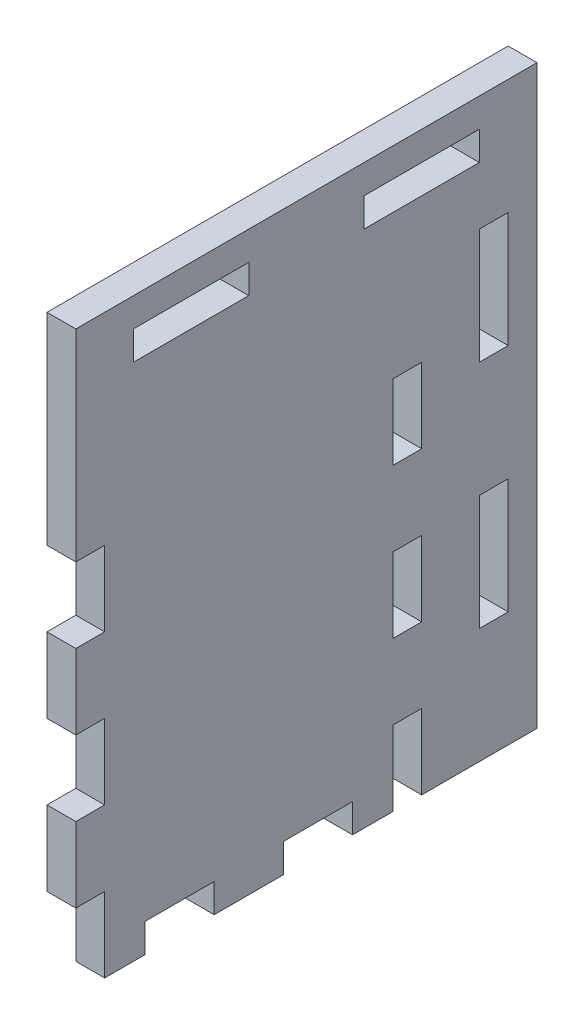
SolidWorks part; units mm, degrees
ref_plane "Plan de face" through (0, 0, 0) normal (0, 0, 1) x (1, 0, 0)
ref_plane "Plan de dessus" through (0, 0, 0) normal (0, 1, 0) x (1, 0, 0)
ref_plane "Plan de droite" through (0, 0, 0) normal (1, 0, 0) x (0, 0, -1)
sketch "Esquisse1" plane through (0, 0, 0) normal (1, 0, 0) x (0, 0, -1)
  line L0 (0, 0) -> (0, 35)
  line L2 (0, 0) -> (0, -65)
  line L3 (0, -65) -> (60, -65)
  line L4 (60, 0) -> (60, -65)
  line L5 (0, 35) -> (45, 35)
  line L7 (45, 0) -> (60, 0)
  line L8 (45, 0) -> (45, 35)
  dimension "D1" = 60
  dimension "D2" = 65
  dimension "D3" = 35
  dimension "D4" = 15
extrude "Boss.-Extru.1" add sketch "Esquisse1" along normal blind 5
sketch "Esquisse2" plane through (5, 0, 0) normal (1, 0, 0) x (0, 0, -1)
  line L0 (0, -65) -> (60, -65) construction
  line L1 (12, -65) -> (24, -65)
  line L2 (12, -65) -> (12, -60)
  line L3 (12, -60) -> (24, -60)
  line L4 (24, -65) -> (24, -60)
  line L5 (0, -65) -> (60, -65) construction
  line L6 (0, 35) -> (0, -65) construction
  dimension "D1" = 60
  dimension "D2" = 12
  dimension "D3" = 5
  dimension "D4" = 12
extrude "Enlèv. mat.-Extru.1" cut sketch "Esquisse2" against normal blind 5
pattern_linear "Répétition linéaire1" count 2 spacing 24 along (0, 0, -1) of "Enlèv. mat.-Extru.1"
ref_plane "Plan1" through (0, 0, -30) normal (0, 0, 1) x (1, 0, 0)
sketch "Esquisse4" plane through (5, 0, 0) normal (1, 0, 0) x (0, 0, -1)
  line L0 (60, 0) -> (60, -65) construction
  line L1 (0, -65) -> (5, -65)
  line L2 (0, -65) -> (0, -52)
  line L3 (0, -52) -> (5, -52)
  line L4 (5, -65) -> (5, -52)
  dimension "D3" = 5
  dimension "D1" = 65
  dimension "D2" = 13
extrude "Enlèv. mat.-Extru.2" cut sketch "Esquisse4" against normal blind 5
pattern_linear "Répétition linéaire2" count 3 spacing 26 along (0, 1, 0) of "Enlèv. mat.-Extru.2"
mirror "Symétrie1" about plane through (0, 0, -30) normal (0, 0, 1) of "Répétition linéaire2"
sketch "Esquisse5" plane through (5, 0, 0) normal (1, 0, 0) x (0, 0, -1)
  line L0 (45, 0) -> (60, 0)
  line L2 (60, 0) -> (60, -65)
  line L3 (60, -65) -> (80, -65)
  line L5 (45, 0) -> (45, 35)
  line L6 (45, 35) -> (80, 35)
  line L8 (80, -65) -> (80, 35)
  line L9 (48, -65) -> (55, -65) construction
  line L10 (60, -52) -> (60, -39) construction
  dimension "D1" = 20
extrude "Boss.-Extru.3" add sketch "Esquisse5" against normal blind 5
ref_plane "Plan2" through (0, 0, -40) normal (0, 0, 1) x (1, 0, 0)
ref_plane "Plan3" through (0, -15, 0) normal (0, 1, 0) x (1, 0, 0)
sketch "Esquisse7" plane through (5, 0, 0) normal (1, 0, 0) x (0, 0, -1)
  line L1 (10, 30) -> (30, 30)
  line L2 (10, 30) -> (10, 25)
  line L3 (10, 25) -> (30, 25)
  line L4 (30, 30) -> (30, 25)
  line L5 (40, 2.75) -> (40, -2.75) construction
  line L6 (80, 35) -> (0, 35) construction
  line L7 (40, 35) -> (40, 10.2809) construction
  line L8 (50, 30) -> (50, 25)
  line L9 (70, 25) -> (50, 25)
  line L10 (70, 30) -> (70, 25)
  line L11 (70, 30) -> (50, 30)
  point P4 (30, 27.5)
  dimension "D1" = 20
  dimension "D2" = 5
  dimension "D3" = 10
  dimension "D4" = 5
extrude "Enlèv. mat.-Extru.3" cut sketch "Esquisse7" against normal blind 5
sketch "Esquisse8" plane through (5, 0, 0) normal (1, 0, 0) x (0, 0, -1)
  line L0 (2.75, -15) -> (-2.75, -15) construction
  line L1 (75, -5) -> (70, -5)
  line L2 (75, -5) -> (75, 15)
  line L3 (75, 15) -> (70, 15)
  line L4 (70, -5) -> (70, 15)
  line L5 (80, -65) -> (80, 35) construction
  line L6 (80, -15) -> (65.6039, -15) construction
  line L7 (70, -25) -> (70, -45)
  line L8 (75, -45) -> (70, -45)
  line L9 (75, -25) -> (75, -45)
  line L10 (75, -25) -> (70, -25)
  point P4 (72.5, -5)
  dimension "D1" = 20
  dimension "D2" = 5
  dimension "D3" = 10
  dimension "D4" = 5
extrude "Enlèv. mat.-Extru.4" cut sketch "Esquisse8" against normal blind 5
equation "\"D2@Esquisse2\"=\"D1@Esquisse2\"/5"
equation "\"D4@Esquisse2\"=\"D2@Esquisse2\""
equation "\"D2@Esquisse4\"=\"D1@Esquisse4\"/5"
equation "\"D3@Esquisse7\"=\"D1@Esquisse7\"/2"
equation "\"D3@Esquisse8\"=\"D1@Esquisse8\"/2"
